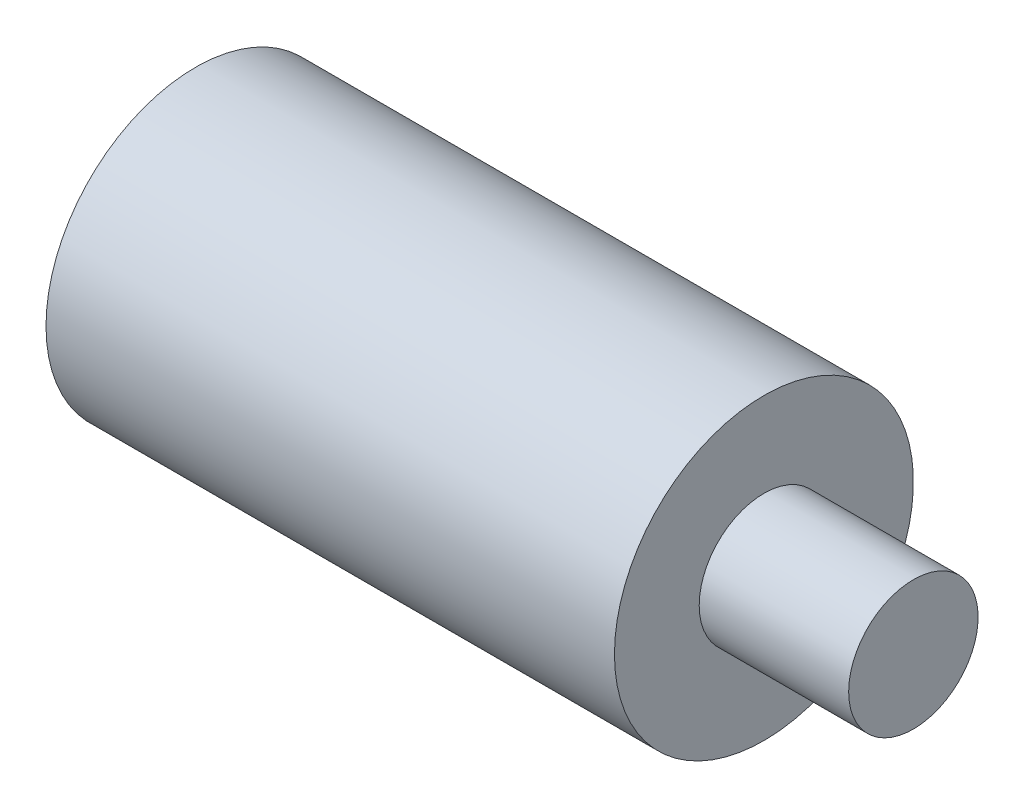
SolidWorks part; units mm, degrees
ref_plane "Front Plane" through (0, 0, 0) normal (0, 0, 1) x (1, 0, 0)
ref_plane "Top Plane" through (0, 0, 0) normal (0, 1, 0) x (1, 0, 0)
ref_plane "Right Plane" through (0, 0, 0) normal (1, 0, 0) x (0, 0, -1)
sketch "CV_Nuvair Sketch" plane through (0, 0, 0) normal (0, 0, 1) x (1, 0, 0)
  line L0 (-1000, 0) -> (1000, 0) construction
  line L1 (12.7, 0) -> (12.7, 5.5)
  line L2 (12.7, 5.5) -> (0, 5.5)
  line L3 (0, 5.5) -> (0, 12.7)
  line L4 (0, 12.7) -> (-48.3, 12.7)
  line L5 (-48.3, 12.7) -> (-48.3, 0)
  line L6 (-48.3, 0) -> (12.7, 0)
revolve "CV_Nuvair" add sketch "CV_Nuvair Sketch" angle 360 about L0
ref_axis "Engine Axis" through (15.75, 0, 0) along (-1, 0, 0)
sketch "Socket 1 Sketch" plane through (0, 0, 0) normal (0, 0, 1) x (1, 0, 0)
  line L0 (-1000, 0) -> (1000, 0) construction
  line L1 (-49.3, 0) -> (-49.3, 5.5)
  line L2 (-49.3, 5.5) -> (-34.3, 5.5)
  line L3 (-34.3, 5.5) -> (-34.3, 0)
  line L4 (-34.3, 0) -> (-49.3, 0)
revolve "Socket 1" cut sketch "Socket 1 Sketch" angle 360 about L0
